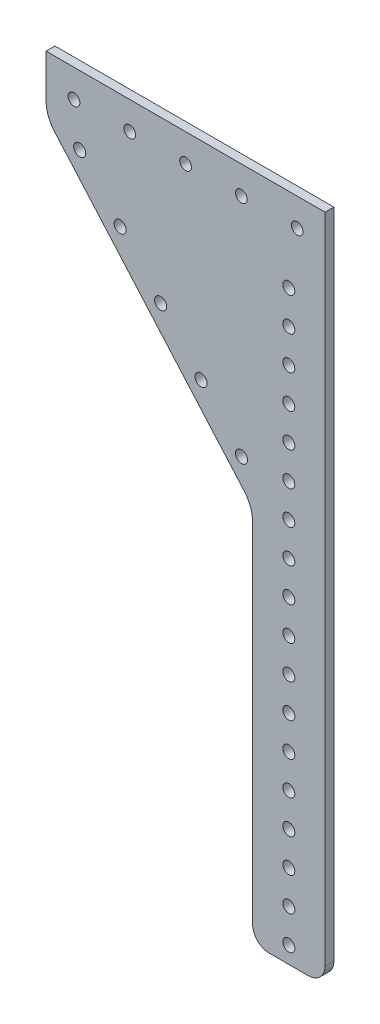
SolidWorks part; units mm, degrees
ref_plane "Front Plane" through (0, 0, 0) normal (0, 0, 1) x (1, 0, 0)
ref_plane "Top Plane" through (0, 0, 0) normal (0, 1, 0) x (1, 0, 0)
ref_plane "Right Plane" through (0, 0, 0) normal (1, 0, 0) x (0, 0, -1)
sketch "Sketch1" plane through (0, 0, 0) normal (0, 0, 1) x (1, 0, 0)
  line L0 (26, 240) -> (26, 0)
  line L1 (0, 0) -> (26, 0)
  line L2 (0, 0) -> (0, 220) construction
  line L5 (0, 220) -> (-74, 220) construction
  line L7 (26, 240) -> (-74, 240)
  line L8 (-74, 220) -> (-74, 240)
  line L9 (-74, 230) -> (26, 230) construction
  line L10 (-74, 220) -> (0, 135.5445)
  line L11 (0, 135.5445) -> (0, 0)
  line L12 (-66.0226, 220) -> (0, 144.649) construction
  circle A0 centre (13, 6) radius 2.15
  circle A1 centre (13, 18) radius 2.15
  circle A2 centre (13, 30) radius 2.15
  circle A3 centre (13, 42) radius 2.15
  circle A4 centre (13, 54) radius 2.15
  circle A5 centre (13, 66) radius 2.15
  circle A6 centre (13, 78) radius 2.15
  circle A7 centre (13, 90) radius 2.15
  circle A8 centre (13, 102) radius 2.15
  circle A9 centre (13, 114) radius 2.15
  circle A10 centre (13, 126) radius 2.15
  circle A11 centre (13, 138) radius 2.15
  circle A12 centre (13, 150) radius 2.15
  circle A13 centre (13, 162) radius 2.15
  circle A14 centre (13, 174) radius 2.15
  circle A15 centre (13, 186) radius 2.15
  circle A16 centre (13, 198) radius 2.15
  circle A17 centre (13, 210) radius 2.15
  circle A19 centre (16, 230) radius 2.1
  circle A20 centre (-4, 230) radius 2.1
  circle A21 centre (-24, 230) radius 2.1
  circle A22 centre (-44, 230) radius 2.1
  circle A23 centre (-64, 230) radius 2.1
  circle A24 centre (-3.9541, 149.1617) radius 2.15
  circle A25 centre (-18.4524, 165.7086) radius 2.15
  circle A26 centre (-32.9508, 182.2554) radius 2.15
  circle A27 centre (-47.4492, 198.8022) radius 2.15
  circle A28 centre (-61.9475, 215.3491) radius 2.15
  point P60 (0, 132.1483)
  point P61 (0, 135.5445)
  dimension "D5" = 4.3
  dimension "D7" = 10
  dimension "D8" = 4.2
  dimension "D11" = 4.3
  dimension "D1" = 26
  dimension "D2" = 20
  dimension "D3" = 100
  dimension "D4" = 240
  dimension "D6" = 6
  dimension "D9" = 10
  dimension "D10" = 6
  dimension "D12" = 6
  dimension "D13" = 22
extrude "Boss-Extrude1" add sketch "Sketch1" along normal blind 3.175
fillet "Fillet2" radius 12 2 edges at (0, 135.5445, 1.5875) (-74, 220, 1.5875)
fillet "Fillet3" radius 6 2 edges at (26, 0, 1.5875) (0, 0, 1.5875)
